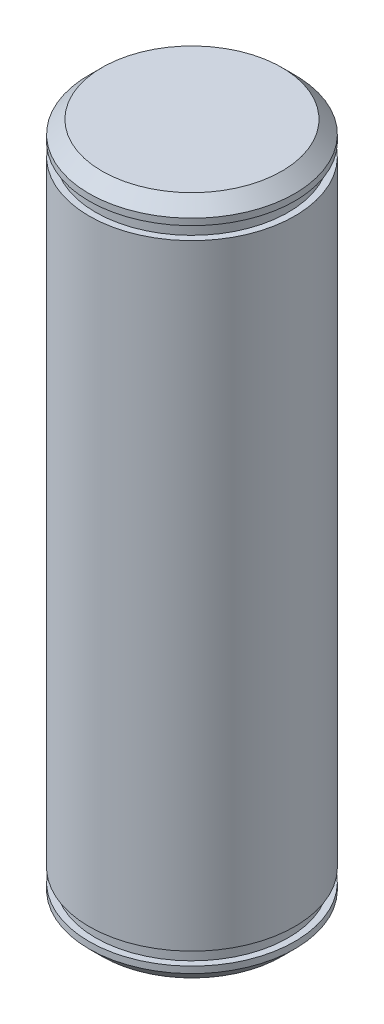
SolidWorks part; units mm, degrees
ref_plane "Front Plane" through (0, 0, 0) normal (0, 0, 1) x (1, 0, 0)
ref_plane "Top Plane" through (0, 0, 0) normal (0, 1, 0) x (1, 0, 0)
ref_plane "Right Plane" through (0, 0, 0) normal (1, 0, 0) x (0, 0, -1)
sketch "Sketch1" plane through (0, 0, 0) normal (0, 1, 0) x (1, 0, 0)
  circle A0 centre (0, 0) radius 14.875
  circle A1 centre (0, 0) radius 15.875
  dimension "D1" = 29.75
  dimension "D2" = 31.75
extrude "Boss-Extrude1" add sketch "Sketch1" along normal blind 105 contours A0 | A1 A0 region at (0, 0, 0) region at (-15.426, 0, 0)
chamfer "Chamfer1" distance 2 angle 45 2 edges at (0, 0, 15.875) (0, 105, 15.875)
extrude "Cut-Extrude1" cut sketch "Sketch1<3>" along normal blind 2 from offset 3
sketch "Sketch1<3>" plane through (0, 0, 0) normal (0, 1, 0) x (1, 0, 0) same geometry as "Sketch1"
ref_plane "Plane1" through (0, 52.5, 0) normal (0, -1, 0) x (-1, 0, 0)
mirror "Mirror1" about plane through (0, 52.5, 0) normal (0, -1, 0) of "Cut-Extrude1"
